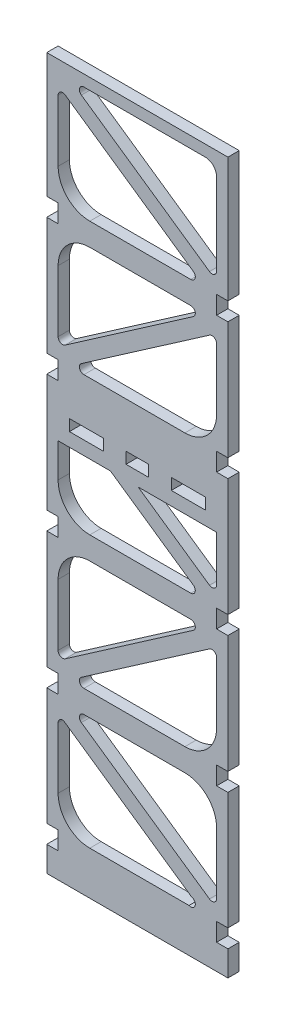
SolidWorks part; units mm, degrees
material "Balsa"
ref_plane "Front Plane" through (0, 0, 0) normal (0, 0, 1) x (1, 0, 0)
ref_plane "Top Plane" through (0, 0, 0) normal (0, 1, 0) x (1, 0, 0)
ref_plane "Right Plane" through (0, 0, 0) normal (1, 0, 0) x (0, 0, -1)
sketch "Model" plane through (0, 0, 0) normal (0, 0, 1) x (1, 0, 0)
  line L0 (77.47, 87.63) -> (20.8312, 87.63)
  line L1 (95.25, 35.3278) -> (95.25, 69.85)
  line L2 (19.3854, 83.0016) -> (91.2642, 33.2394)
  line L3 (6.35, 146.05) -> (6.35, 111.5278)
  line L4 (80.7688, 163.83) -> (24.13, 163.83)
  line L5 (10.3358, 109.4394) -> (82.2146, 159.2016)
  line L6 (77.47, 240.03) -> (20.8312, 240.03)
  line L7 (95.25, 187.7278) -> (95.25, 222.25)
  line L8 (19.3854, 235.4016) -> (91.2642, 185.6394)
  line L9 (24.13, 176.53) -> (80.7688, 176.53)
  line L10 (6.35, 228.8322) -> (6.35, 194.31)
  line L11 (82.2146, 181.1584) -> (10.3358, 230.9206)
  line L12 (91.2642, 154.7206) -> (19.3854, 104.9584)
  line L13 (95.25, 118.11) -> (95.25, 152.6322)
  line L14 (20.8312, 100.33) -> (77.47, 100.33)
  line L15 (6.35, 298.45) -> (6.35, 263.9278)
  line L16 (80.7688, 316.23) -> (24.13, 316.23)
  line L17 (10.3358, 261.8394) -> (82.2146, 311.6016)
  line L18 (88.9, 392.43) -> (20.8312, 392.43)
  line L19 (95.25, 340.1278) -> (95.25, 386.08)
  line L20 (19.3854, 387.8016) -> (91.2642, 338.0394)
  line L21 (24.13, 328.93) -> (80.7688, 328.93)
  line L22 (6.35, 381.2322) -> (6.35, 346.71)
  line L23 (82.2146, 333.5584) -> (10.3358, 383.3206)
  line L24 (24.13, 24.3357) -> (79.7674, 24.3357)
  line L25 (6.35, 76.4322) -> (6.35, 42.1157)
  line L26 (81.3163, 29.1503) -> (9.4375, 78.9125)
  line L27 (91.2642, 307.1206) -> (19.3854, 257.3584)
  line L28 (95.25, 270.51) -> (95.25, 305.0322)
  line L29 (20.8312, 252.73) -> (77.47, 252.73)
  line L30 (0, 398.78) -> (0, 0)
  line L31 (0, 0) -> (101.6, 0)
  line L32 (101.6, 398.78) -> (101.6, 0)
  line L33 (0, 398.78) -> (101.6, 398.78)
  arc A1 (91.2642, 33.2394) -> (95.25, 35.3278) centre (92.71, 35.3278) ccw
  arc A2 (20.8312, 87.63) -> (19.3854, 83.0016) centre (20.8312, 85.09) ccw
  arc A4 (82.2146, 159.2016) -> (80.7688, 163.83) centre (80.7688, 161.29) ccw
  arc A5 (6.35, 111.5278) -> (10.3358, 109.4394) centre (8.89, 111.5278) ccw
  arc A7 (91.2642, 185.6394) -> (95.25, 187.7278) centre (92.71, 187.7278) ccw
  arc A8 (20.8312, 240.03) -> (19.3854, 235.4016) centre (20.8312, 237.49) ccw
  arc A10 (10.3358, 230.9206) -> (6.35, 228.8322) centre (8.89, 228.8322) ccw
  arc A11 (80.7688, 176.53) -> (82.2146, 181.1584) centre (80.7688, 179.07) ccw
  arc A12 (95.25, 152.6322) -> (91.2642, 154.7206) centre (92.71, 152.6322) ccw
  arc A14 (19.3854, 104.9584) -> (20.8312, 100.33) centre (20.8312, 102.87) ccw
  arc A16 (82.2146, 311.6016) -> (80.7688, 316.23) centre (80.7688, 313.69) ccw
  arc A17 (6.35, 263.9278) -> (10.3358, 261.8394) centre (8.89, 263.9278) ccw
  arc A18 (95.25, 386.08) -> (88.9, 392.43) centre (88.9, 386.08) ccw
  arc A19 (91.2642, 338.0394) -> (95.25, 340.1278) centre (92.71, 340.1278) ccw
  arc A20 (20.8312, 392.43) -> (19.3854, 387.8016) centre (20.8312, 389.89) ccw
  arc A22 (10.3358, 383.3206) -> (6.35, 381.2322) centre (8.89, 381.2322) ccw
  arc A23 (80.7688, 328.93) -> (82.2146, 333.5584) centre (80.7688, 331.47) ccw
  arc A25 (9.4375, 78.9125) -> (6.35, 76.4322) centre (8.89, 76.4322) ccw
  arc A26 (79.7674, 24.3357) -> (81.3163, 29.1503) centre (80.7688, 26.67) ccw
  arc A27 (95.25, 305.0322) -> (91.2642, 307.1206) centre (92.71, 305.0322) ccw
  arc A29 (19.3854, 257.3584) -> (20.8312, 252.73) centre (20.8312, 255.27) ccw
  arc A30 (6.35, 42.1157) -> (24.13, 24.3357) centre (24.13, 42.1157) ccw
  arc A31 (6.35, 346.71) -> (24.13, 328.93) centre (24.13, 346.71) ccw
  arc A32 (6.35, 298.45) -> (24.13, 316.23) centre (24.13, 298.45) cw
  arc A33 (95.25, 270.51) -> (77.47, 252.73) centre (77.47, 270.51) cw
  arc A34 (77.47, 240.03) -> (95.25, 222.25) centre (77.47, 222.25) cw
  arc A35 (6.35, 194.31) -> (24.13, 176.53) centre (24.13, 194.31) ccw
  arc A36 (6.35, 146.05) -> (24.13, 163.83) centre (24.13, 146.05) cw
  arc A37 (77.47, 100.33) -> (95.25, 118.11) centre (77.47, 118.11) ccw
  arc A38 (77.47, 87.63) -> (95.25, 69.85) centre (77.47, 69.85) cw
  dimension "D3" = 6.35
  dimension "D4" = 2.54
  dimension "D5" = 2.54
  dimension "D6" = 2.54
  dimension "D7" = 2.54
  dimension "D8" = 2.54
  dimension "D9" = 2.54
  dimension "D10" = 2.54
  dimension "D11" = 2.54
  dimension "D12" = 2.54
  dimension "D13" = 2.54
  dimension "D14" = 2.54
  dimension "D15" = 2.54
  dimension "D16" = 2.54
  dimension "D17" = 2.54
  dimension "D18" = 2.54
  dimension "D19" = 2.54
  dimension "D20" = 2.54
  dimension "D21" = 2.54
  dimension "D22" = 2.54
  dimension "D26" = 17.78
  dimension "D27" = 17.78
  dimension "D1" = 398.78
  dimension "D2" = 101.6
  dimension "D23" = 26.67
  dimension "D24" = 20.8312
  dimension "D25" = 87.4233
extrude "Boss-Extrude1" add sketch "Model" along normal blind 6.35
sketch "Sketch1" plane through (0, 0, 6.35) normal (0, 0, 1) x (1, 0, 0)
  line L0 (101.6, 0) -> (101.6, 398.78) construction
  line L1 (101.6, 328.93) -> (95.25, 328.93)
  line L2 (101.6, 328.93) -> (101.6, 318.77)
  line L3 (101.6, 318.77) -> (95.25, 318.77)
  line L4 (95.25, 328.93) -> (95.25, 318.77)
  line L5 (0, 398.78) -> (0, 0) construction
  line L6 (0, 252.73) -> (6.35, 252.73)
  line L7 (0, 252.73) -> (0, 242.57)
  line L8 (0, 242.57) -> (6.35, 242.57)
  line L9 (6.35, 252.73) -> (6.35, 242.57)
  line L10 (24.13, 328.93) -> (80.7688, 328.93) construction
  line L11 (101.6, 176.53) -> (95.25, 176.53)
  line L12 (101.6, 176.53) -> (101.6, 166.37)
  line L13 (101.6, 166.37) -> (95.25, 166.37)
  line L14 (95.25, 176.53) -> (95.25, 166.37)
  line L15 (0, 100.33) -> (6.35, 100.33)
  line L16 (0, 100.33) -> (0, 90.17)
  line L17 (0, 90.17) -> (6.35, 90.17)
  line L18 (6.35, 100.33) -> (6.35, 90.17)
  line L19 (20.8312, 252.73) -> (77.47, 252.73) construction
  line L21 (20.8312, 100.33) -> (77.47, 100.33) construction
  line L22 (24.13, 24.3357) -> (79.7674, 24.3357) construction
  line L23 (0, 328.93) -> (6.35, 328.93)
  line L24 (0, 328.93) -> (0, 318.77)
  line L25 (0, 318.77) -> (6.35, 318.77)
  line L26 (6.35, 328.93) -> (6.35, 318.77)
  line L27 (101.6, 252.73) -> (95.25, 252.73)
  line L28 (101.6, 252.73) -> (101.6, 242.57)
  line L29 (101.6, 242.57) -> (95.25, 242.57)
  line L30 (95.25, 252.73) -> (95.25, 242.57)
  line L31 (0, 176.53) -> (6.35, 176.53)
  line L32 (0, 176.53) -> (0, 166.37)
  line L33 (0, 166.37) -> (6.35, 166.37)
  line L34 (6.35, 176.53) -> (6.35, 166.37)
  line L35 (101.6, 100.33) -> (95.25, 100.33)
  line L36 (101.6, 100.33) -> (101.6, 90.17)
  line L37 (101.6, 90.17) -> (95.25, 90.17)
  line L38 (95.25, 100.33) -> (95.25, 90.17)
  line L39 (0, 24.3357) -> (6.35, 24.3357)
  line L40 (0, 24.3357) -> (0, 14.1757)
  line L41 (0, 14.1757) -> (6.35, 14.1757)
  line L42 (6.35, 24.3357) -> (6.35, 14.1757)
  line L43 (101.6, 24.3357) -> (95.25, 24.3357)
  line L44 (101.6, 24.3357) -> (101.6, 14.1757)
  line L45 (101.6, 14.1757) -> (95.25, 14.1757)
  line L46 (95.25, 24.3357) -> (95.25, 14.1757)
  line L47 (24.13, 176.53) -> (80.7688, 176.53) construction
  dimension "D1" = 6.35
  dimension "D2" = 10.16
  dimension "D3" = 10.16
  dimension "D4" = 6.35
  dimension "D5" = 6.35
  dimension "D6" = 10.16
  dimension "D7" = 6.35
  dimension "D8" = 10.16
  dimension "D9" = 10.16
  dimension "D10" = 10.16
extrude "Cut-Extrude1" cut sketch "Sketch1" against normal up to surface (6.35 mm away) contours L1 L4 L3 L2 | L27 L30 L29 L28 | L9 L6 L7 L8 | L42 L39 L40 L41 | L11 L14 L13 L12 | L26 L25 L24 L23 | L43 L46 L45 L44 | L38 L37 L36 L35 | L15 L18 L17 L16 | L31 L34 L33 L32 region at (98.425, 323.85, 6.35) region at (3.175, 247.65, 6.35) region at (98.425, 171.45, 6.35) region at (98.425, 247.65, 6.35) region at (3.175, 19.2557, 6.35) up to face at (50.8, 199.39, 0)
sketch "Sketch2" plane through (0, 0, 6.35) normal (0, 0, 1) x (1, 0, 0)
  line L0 (77.47, 240.03) -> (20.8312, 240.03) construction
  line L1 (1.7778, 240.03) -> (97.5543, 240.03)
  line L2 (1.7778, 240.03) -> (1.7778, 213.36)
  line L3 (1.7778, 213.36) -> (97.5543, 213.36)
  line L4 (97.5543, 240.03) -> (97.5543, 213.36)
  dimension "D1" = 26.67
extrude "Boss-Extrude2" add sketch "Sketch2" against normal up to surface (6.35 mm away) up to face at (50.8, 174.0274, 0)
sketch "Sketch3" plane through (0, 0, 6.35) normal (0, 0, 1) x (1, 0, 0)
  line L1 (88.9, 227.33) -> (69.85, 227.33)
  line L2 (88.9, 227.33) -> (88.9, 220.98)
  line L3 (88.9, 220.98) -> (69.85, 220.98)
  line L4 (69.85, 227.33) -> (69.85, 220.98)
  line L5 (101.6, 176.53) -> (101.6, 242.57) construction
  line L6 (0, 242.57) -> (0, 176.53) construction
  line L7 (31.75, 220.98) -> (12.7, 220.98)
  line L8 (31.75, 220.98) -> (31.75, 227.33)
  line L9 (31.75, 227.33) -> (12.7, 227.33)
  line L10 (12.7, 220.98) -> (12.7, 227.33)
  line L12 (6.35, 213.36) -> (35.7011, 213.36) construction
  line L13 (57.15, 220.98) -> (44.45, 220.98)
  line L14 (57.15, 220.98) -> (57.15, 227.33)
  line L15 (57.15, 227.33) -> (44.45, 227.33)
  line L16 (44.45, 220.98) -> (44.45, 227.33)
  line L17 (51.2233, 213.36) -> (95.25, 213.36) construction
  dimension "D2" = 6.35
  dimension "D3" = 12.7
  dimension "D4" = 19.05
  dimension "D5" = 12.7
  dimension "D6" = 19.05
  dimension "D7" = 6.35
  dimension "D8" = 7.62
  dimension "D9" = 12.7
  dimension "D10" = 12.7
  dimension "D11" = 7.62
extrude "Cut-Extrude2" cut sketch "Sketch3" against normal up to surface (6.35 mm away) up to face at (83.4048, 199.7204, 0)
equation "\"thick\"=0.25"
equation "\"D1@Boss-Extrude1\"=\"thick\""
